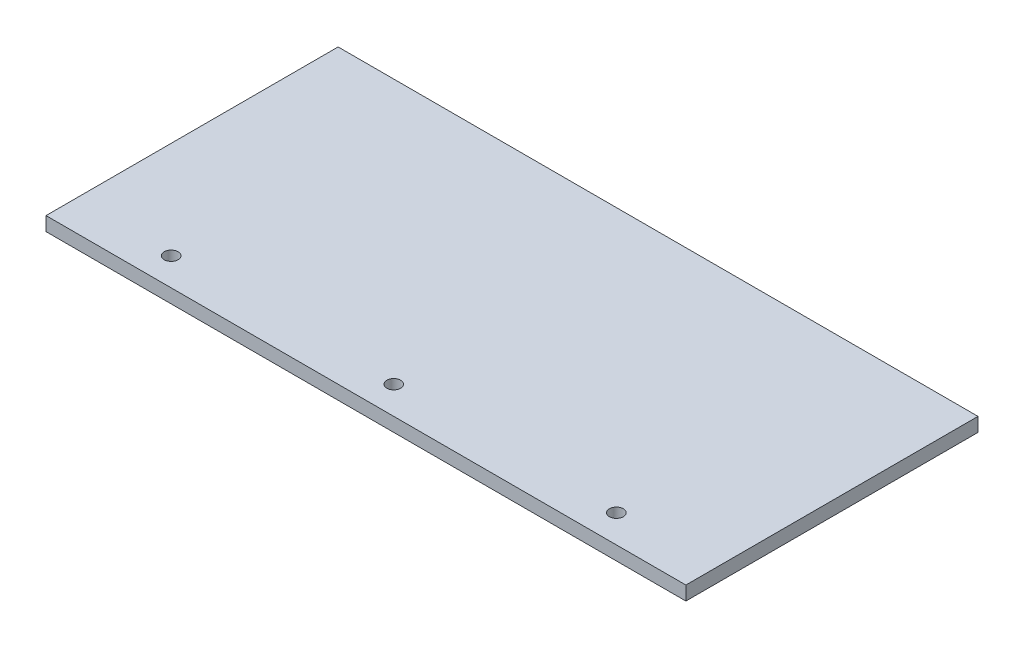
SolidWorks part; units mm, degrees
ref_plane "Front Plane" through (0, 0, 0) normal (0, 0, 1) x (1, 0, 0)
ref_plane "Top Plane" through (0, 0, 0) normal (0, 1, 0) x (1, 0, 0)
ref_plane "Right Plane" through (0, 0, 0) normal (1, 0, 0) x (0, 0, -1)
sketch "Sketch1" plane through (0, 0, 0) normal (0, 1, 0) x (1, 0, 0)
  line L1 (0, 0) -> (292.1, 0)
  line L2 (0, 0) -> (0, 133.35)
  line L3 (0, 133.35) -> (292.1, 133.35)
  line L4 (292.1, 0) -> (292.1, 133.35)
  dimension "D1" = 292.1
  dimension "D2" = 133.35
extrude "Boss-Extrude1" add sketch "Sketch1" along normal blind 6.35
sketch "Sketch2" plane through (0, 6.35, 0) normal (0, 1, 0) x (1, 0, 0)
  line L0 (0, 25.4) -> (292.1, 25.4) construction
  line L1 (0, 12.7) -> (292.1, 12.7) construction
  line L2 (146.05, 0) -> (146.05, 133.35) construction
  line L4 (0, 133.35) -> (0, 0)
  line L5 (0, 0) -> (292.1, 0)
  line L6 (292.1, 0) -> (292.1, 133.35)
  line L7 (292.1, 133.35) -> (0, 133.35)
  line L8 (0, 133.35) -> (0, 0) construction
  line L9 (0, 0) -> (292.1, 0) construction
  line L10 (292.1, 0) -> (292.1, 133.35) construction
  line L11 (292.1, 133.35) -> (0, 133.35) construction
  circle A0 centre (146.05, 12.7) radius 3.175
  circle A1 centre (247.65, 12.7) radius 3.175
  circle A2 centre (44.45, 12.7) radius 3.175
  dimension "D6" = 6.35
  dimension "D7" = 6.35
  dimension "D8" = 6.35
  dimension "D2" = 25.4
  dimension "D3" = 12.7
  dimension "D4" = 101.6
  dimension "D5" = 101.6
  dimension "D1" = 0
extrude "Cut-Extrude2" cut sketch "Sketch2" against normal blind 6.35
equation "\"D5@Sketch2\"=\"D4@Sketch2\""
equation "\"D7@Sketch2\"=\"D6@Sketch2\""
equation "\"D8@Sketch2\"=\"D7@Sketch2\""
